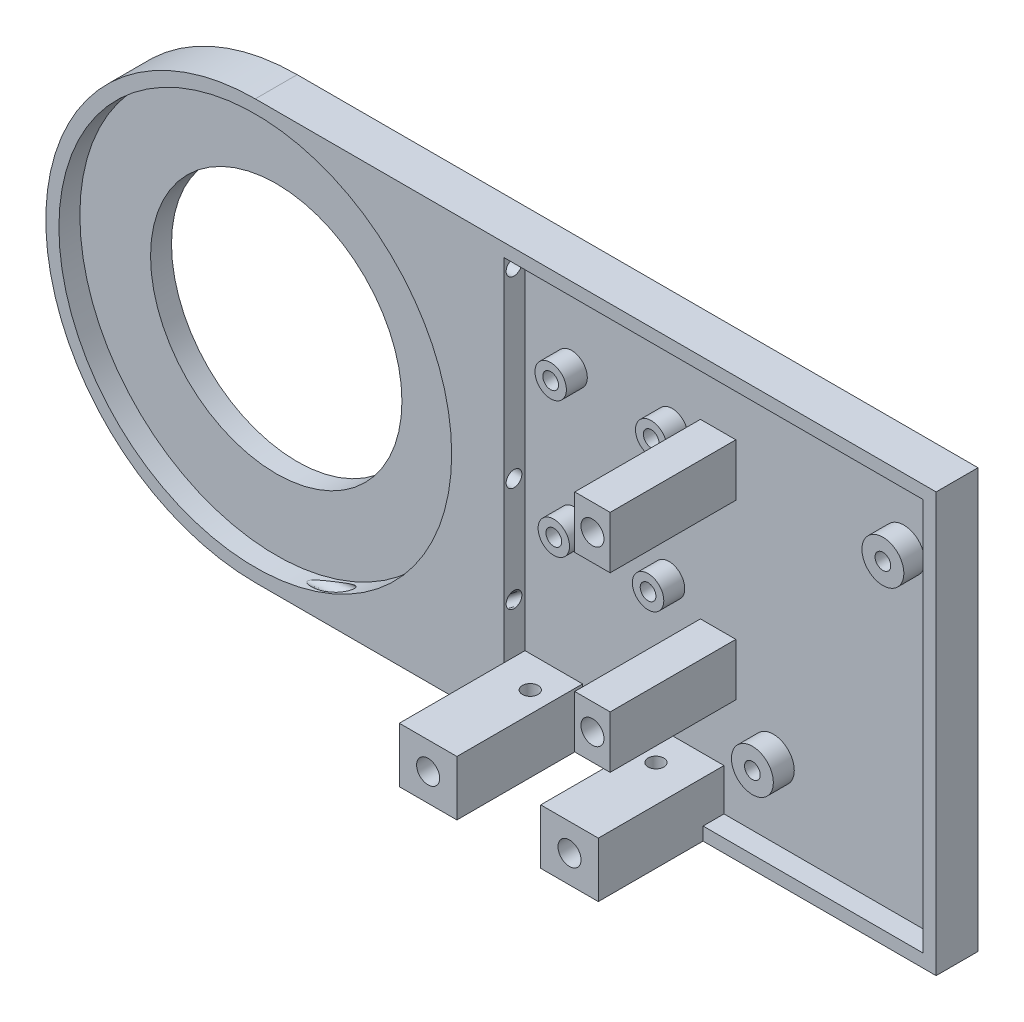
SolidWorks part; units mm, degrees
material "PET"
ref_plane "Front Plane" through (0, 0, 0) normal (0, 0, 1) x (1, 0, 0)
ref_plane "Top Plane" through (0, 0, 0) normal (0, 1, 0) x (1, 0, 0)
ref_plane "Right Plane" through (0, 0, 0) normal (1, 0, 0) x (0, 0, -1)
sketch "Sketch1" plane through (0, 0, 0) normal (0, 0, 1) x (1, 0, 0)
  line L0 (0, 25.4) -> (82.55, 25.4)
  line L1 (82.55, 25.4) -> (82.55, -25.4)
  line L2 (82.55, -25.4) -> (0, -25.4)
  circle A0 centre (0, 0) radius 15.24
  arc A1 (0, 25.4) -> (0, -25.4) centre (0, 0) ccw
  dimension "D1" = 30.48
  dimension "D2" = 25.4
  dimension "D3" = 82.55
extrude "Boss-Extrude1" add sketch "Sketch1" along normal blind 2.54
sketch "Sketch2" plane through (0, 0, 2.54) normal (0, 0, 1) x (1, 0, 0)
  line L3 (82.55, -25.4) -> (82.55, 25.4) construction
  line L4 (0, -25.4) -> (82.55, -25.4) construction
  line L5 (82.55, 25.4) -> (0, 25.4) construction
  line L6 (0, -23.8125) -> (80.9625, -23.8125)
  line L7 (80.9625, -23.8125) -> (80.9625, 23.8125)
  line L8 (80.9625, 23.8125) -> (0, 23.8125)
  line L9 (0, -23.8125) -> (80.9625, -23.8125)
  line L10 (80.9625, -23.8125) -> (80.9625, 23.8125)
  line L11 (80.9625, 23.8125) -> (0, 23.8125)
  line L12 (82.55, -25.4) -> (82.55, 25.4)
  line L13 (0, -25.4) -> (82.55, -25.4)
  line L14 (82.55, 25.4) -> (0, 25.4)
  arc A1 (0, 25.4) -> (0, -25.4) centre (0, 0) ccw construction
  arc A2 (0, 23.8125) -> (0, -23.8125) centre (0, 0) ccw
  arc A3 (0, 23.8125) -> (0, -23.8125) centre (0, 0) ccw
  arc A4 (0, 25.4) -> (0, -25.4) centre (0, 0) ccw
  dimension "D1" = 1.5875
extrude "Boss-Extrude2" add sketch "Sketch2" along normal blind 2.54
sketch "Sketch3" plane through (0, 0, 2.54) normal (0, 0, 1) x (1, 0, 0)
  line L0 (80.9625, 23.8125) -> (0, 23.8125) construction
  line L2 (23.8125, 23.8125) -> (23.8125, -23.8125) construction
  line L4 (30.1625, 23.8125) -> (30.1625, -23.8125)
  line L5 (0, -23.8125) -> (80.9625, -23.8125) construction
  line L6 (23.8125, 0) -> (30.1625, 0) construction
  line L7 (0, -23.8125) -> (30.1625, -23.8125)
  line L8 (0, 23.8125) -> (30.1625, 23.8125)
  circle A1 centre (0, 0) radius 23.8125 construction
  arc A3 (0, -23.8125) -> (0, 23.8125) centre (0, 0) ccw
  dimension "D1" = 6.35
extrude "Boss-Extrude3" add sketch "Sketch3" along normal up to surface (2.54 mm away) contours L4 L7 A3 L8 up to face at (34.925, 0, 5.08)
sketch "Sketch4" plane through (30.1625, 0, 0) normal (1, 0, 0) x (0, 0, -1)
  line L0 (-3.8735, -22.225) -> (-3.8735, 0) construction
  line L1 (-3.8735, 0) -> (-3.8735, 22.225) construction
  line L3 (-5.08, -25.4) -> (0, -25.4) construction
  line L4 (-5.08, 25.4) -> (0, 25.4) construction
  line L5 (-5.08, 0) -> (-4.826, 0) construction
  line L6 (-5.08, -25.4) -> (-5.08, 25.4) construction
  circle A0 centre (-3.8735, 22.225) radius 0.9525
  circle A1 centre (-3.8735, 0) radius 0.9525
  circle A2 centre (-3.8735, -22.225) radius 0.9525 construction
  dimension "D1" = 1.905
  dimension "D2" = 1.905
  dimension "D3" = 1.905
  dimension "D4" = 3.175
  dimension "D5" = 3.175
  dimension "D6" = 25.4
  dimension "D7" = 0.254
extrude "Cut-Extrude1" cut sketch "Sketch4" against normal blind 31.75
sketch "Sketch6" plane through (0, 0, 2.54) normal (0, 0, 1) x (1, 0, 0)
  point P0 (35.814, 13.716)
  point P1 (48.006, 13.716)
  point P3 (76.0984, 14.8844)
  point P5 (60.2742, -14.986)
  point P7 (47.625, -2.54)
  point P9 (36.195, -2.54)
sketch "Sketch8" plane through (0, 0, 2.54) normal (0, 0, 1) x (1, 0, 0)
  circle A0 centre (35.814, 13.716) radius 1.905
  circle A1 centre (48.006, 13.716) radius 1.905
  circle A2 centre (47.625, -2.54) radius 1.905
  circle A3 centre (36.195, -2.54) radius 1.905
  circle A4 centre (76.0984, 14.8844) radius 2.54
  circle A5 centre (60.2742, -14.986) radius 2.54
  dimension "D1" = 5.08
  dimension "D2" = 5.08
  dimension "D3" = 3.81
extrude "Boss-Extrude5" add sketch "Sketch8" along normal blind 2.54
sketch "Sketch9" plane through (0, 0, 5.08) normal (0, 0, 1) x (1, 0, 0)
  circle A0 centre (35.814, 13.716) radius 0.9525
  circle A1 centre (48.006, 13.716) radius 0.9525
  circle A2 centre (36.195, -2.54) radius 0.9525
  circle A3 centre (47.625, -2.54) radius 0.9525
  circle A4 centre (60.2742, -14.986) radius 0.9525
  circle A5 centre (76.0984, 14.8844) radius 0.9525
  dimension "D1" = 1.905
extrude "Cut-Extrude2" cut sketch "Sketch9" against normal blind 3.81
sketch "Sketch10" plane through (0, 0, 2.54) normal (0, 0, 1) x (1, 0, 0)
  line L0 (30.1625, -23.8125) -> (30.1625, -18.7325)
  line L1 (30.1625, 23.8125) -> (30.1625, -23.8125) construction
  line L2 (30.1625, -18.7325) -> (37.1475, -18.7325)
  line L3 (37.1475, -18.7325) -> (37.1475, -23.8125)
  line L4 (30.1625, -23.8125) -> (80.9625, -23.8125) construction
  line L5 (37.1475, -23.8125) -> (30.1625, -23.8125) construction
  line L6 (30.1625, -23.8125) -> (30.1625, -25.4)
  line L7 (47.3075, -23.8125) -> (54.2925, -23.8125) construction
  line L8 (47.3075, -23.8125) -> (47.3075, -18.7325)
  line L9 (47.3075, -18.7325) -> (54.2925, -18.7325)
  line L10 (54.2925, -23.8125) -> (54.2925, -18.7325)
  line L11 (0, -25.4) -> (82.55, -25.4) construction
  line L12 (30.1625, -25.4) -> (37.1475, -25.4)
  line L13 (37.1475, -25.4) -> (37.1475, -23.8125)
  line L14 (47.3075, -23.8125) -> (47.3075, -25.4)
  line L15 (47.3075, -25.4) -> (54.2925, -25.4)
  line L16 (54.2925, -25.4) -> (54.2925, -23.8125)
  dimension "D1" = 6.985
  dimension "D2" = 10.16
  dimension "D3" = 6.985
  dimension "D4" = 5.08
  dimension "D5" = 5.08
extrude "Boss-Extrude6" add sketch "Sketch10" along normal blind 15.24 contours L2 L3 L13 L12 L6 L0 | L9 L10 L16 L15 L14 L8
sketch "Sketch11" plane through (0, 0, 5.08) normal (0, 0, 1) x (1, 0, 0)
  line L0 (0, -25.4) -> (30.1625, -25.4) construction
  line L1 (37.1475, -23.8125) -> (47.3075, -23.8125)
  line L2 (37.1475, -23.8125) -> (37.1475, -25.4)
  line L3 (37.1475, -25.4) -> (47.3075, -25.4)
  line L4 (47.3075, -23.8125) -> (47.3075, -25.4)
  point P7 (47.3075, -23.8125)
extrude "Cut-Extrude3" cut sketch "Sketch11" against normal up to surface (2.54 mm away) up to face at (62.8142, -14.986, 2.54)
sketch "Sketch12" plane through (0, -18.7325, 0) normal (0, 1, 0) x (1, 0, 0)
  line L0 (34.6075, -6.35) -> (49.8475, -6.35) construction
  line L1 (42.2275, -17.78) -> (42.2275, -6.35) construction
  line L4 (37.1475, -17.78) -> (47.3075, -17.78) construction
  line L6 (30.1625, -2.54) -> (37.1475, -2.54) construction
  circle A0 centre (34.6075, -6.35) radius 0.9525
  circle A1 centre (49.8475, -6.35) radius 0.9525
  point P6 (42.2275, -5.9537)
  dimension "D3" = 1.905
  dimension "D1" = 15.24
  dimension "D2" = 3.81
extrude "Cut-Extrude4" cut sketch "Sketch12" against normal offset from surface (6.1595 mm away) 0.508 contours A0 | A1 up to face at (41.91, -25.4, 8.0433)
sketch "Sketch13" plane through (0, 0, 2.54) normal (0, 0, 1) x (1, 0, 0)
  line L0 (49.53, -3.302) -> (49.53, 20.32) construction
  line L1 (51.435, 16.1925) -> (55.7276, 16.1925)
  line L2 (51.435, 16.1925) -> (51.435, -11.1125) construction
  line L3 (51.435, -11.1125) -> (55.7276, -11.1125)
  line L4 (55.7276, 16.1925) -> (55.7276, -11.1125) construction
  line L5 (57.6326, -17.5768) -> (57.6326, 17.5768) construction
  line L6 (80.9625, 23.8125) -> (30.1625, 23.8125) construction
  line L7 (47.3075, -18.7325) -> (54.2925, -18.7325) construction
  line L8 (51.435, 16.1925) -> (51.435, 9.8425)
  line L9 (51.435, 9.8425) -> (55.7276, 9.8425)
  line L10 (55.7276, 9.8425) -> (55.7276, 16.1925)
  line L11 (55.7276, -11.1125) -> (55.7276, -4.7625)
  line L12 (55.7276, -4.7625) -> (51.435, -4.7625)
  line L13 (51.435, -4.7625) -> (51.435, -11.1125)
  dimension "D1" = 1.905
  dimension "D2" = 1.905
  dimension "D3" = 7.62
  dimension "D4" = 7.62
  dimension "D5" = 6.35
  dimension "D6" = 6.35
extrude "Boss-Extrude7" add sketch "Sketch13" along normal blind 15.24
sketch "Sketch14" plane through (0, 0, 17.78) normal (0, 0, 1) x (1, 0, 0)
  line L0 (37.1475, -22.0662) -> (30.1625, -22.0662) construction
  line L1 (37.1475, -25.4) -> (37.1475, -18.7325) construction
  line L2 (30.1625, -25.4) -> (30.1625, -18.7325) construction
  line L3 (47.3075, -22.0662) -> (54.2925, -22.0662) construction
  line L4 (47.3075, -18.7325) -> (47.3075, -25.4) construction
  line L5 (54.2925, -25.4) -> (54.2925, -18.7325) construction
  line L6 (51.435, -7.9375) -> (55.7276, -7.9375) construction
  line L7 (51.435, -4.7625) -> (51.435, -11.1125) construction
  line L8 (55.7276, -11.1125) -> (55.7276, -4.7625) construction
  line L9 (51.435, 13.0175) -> (55.7276, 13.0175) construction
  line L10 (51.435, 16.1925) -> (51.435, 9.8425) construction
  line L11 (55.7276, 9.8425) -> (55.7276, 16.1925) construction
  circle A0 centre (33.655, -22.0662) radius 1.397
  circle A1 centre (50.8, -22.0662) radius 1.397
  circle A2 centre (53.5813, -7.9375) radius 1.397
  circle A3 centre (53.5813, 13.0175) radius 1.397
  point P32 (51.435, 13.0175)
  dimension "D1" = 2.794
extrude "Cut-Extrude5" cut sketch "Sketch14" against normal blind 10.16
ref_plane "Plane1" through (0, 0, 3.8735) normal (0, 0, 1) x (1, 0, 0)
sketch "Sketch16" plane through (0, 0, 3.8735) normal (0, 0, 1) x (1, 0, 0)
  line L0 (30.1625, -22.225) -> (30.1625, 0) construction
  spline S0 degree 3 poles (0, -22.606) (13.5726, -22.606) (19.8645, -20.8394) (30.1625, -12.7) knots 0 0 0 0 1 1 1 1
  point P6 (30.1625, -13.0549)
  dimension "D1" = 2.794
  dimension "D2" = 12.7
sketch "Sketch17" plane through (30.1625, 0, 0) normal (1, 0, 0) x (0, 0, -1)
  circle A0 centre (-3.8735, -12.7) radius 0.9525
  point P3 (-3.213, -12.522)
  point P4 (0, 0)
  dimension "D1" = 1.905
sweep "Cut-Sweep1" cut profiles "Sketch17" path "Sketch16"
